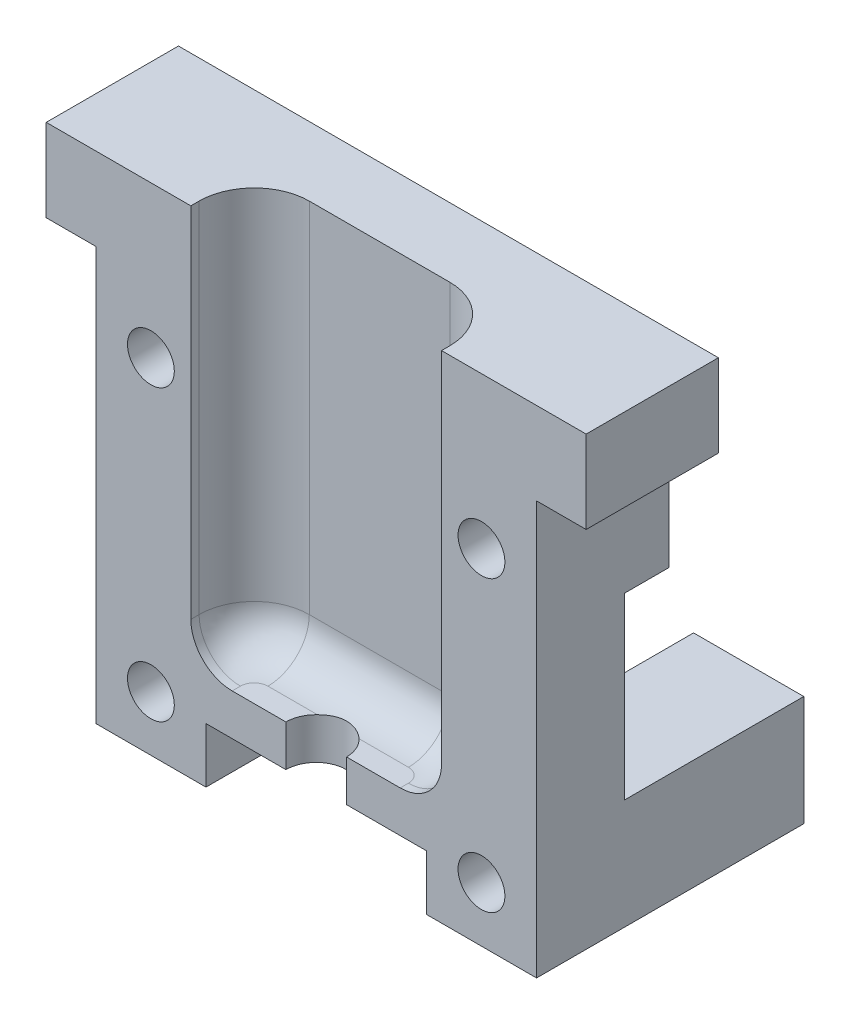
SolidWorks part; units mm, degrees
ref_plane "Спереди" through (0, 0, 0) normal (0, 0, 1) x (1, 0, 0)
ref_plane "Сверху" through (0, 0, 0) normal (0, 1, 0) x (1, 0, 0)
ref_plane "Справа" through (0, 0, 0) normal (1, 0, 0) x (0, 0, -1)
sketch "Эскиз1" plane through (0, 0, 0) normal (0, 0, 1) x (1, 0, 0)
  line L0 (0, 16) -> (0, -16) construction
  line L1 (8, -16) -> (-8, -16)
  line L2 (16, -16) -> (16, 16)
  line L3 (16, 16) -> (-16, 16)
  line L4 (-16, -16) -> (-16, 16)
  line L5 (16, -16) -> (-16, 16) construction
  line L6 (16, 16) -> (-16, -16) construction
  line L7 (-8, -16) -> (-8, -20)
  line L8 (16, -16) -> (16, -20)
  line L9 (16, -20) -> (8, -20)
  line L10 (8, -16) -> (8, -20)
  line L11 (-16, -20) -> (-8, -20)
  line L12 (-16, -16) -> (-16, -20)
  point P0 (0, 0)
  dimension "D1" = 32
  dimension "D2" = 32
  dimension "D3" = 8
  dimension "D4" = 4
extrude "Бобышка-Вытянуть1" add sketch "Эскиз1" along normal blind 16
sketch "Эскиз2" plane through (0, 16, 0) normal (0, 1, 0) x (1, 0, 0)
  line L1 (5.1, -11) -> (-5.1, -11)
  line L2 (9.1, -7) -> (9.1, -5.8)
  line L3 (5.1, -1.8) -> (-5.1, -1.8)
  line L4 (-9.1, -7) -> (-9.1, -5.8)
  line L5 (9.1, -11) -> (-9.1, -1.8) construction
  line L6 (9.1, -1.8) -> (-9.1, -11) construction
  line L7 (16, -16) -> (-16, -16) construction
  arc A0 (5.1, -1.8) -> (9.1, -5.8) centre (5.1, -5.8) cw
  arc A1 (9.1, -7) -> (5.1, -11) centre (5.1, -7) cw
  arc A2 (-5.1, -11) -> (-9.1, -7) centre (-5.1, -7) cw
  arc A3 (-9.1, -5.8) -> (-5.1, -1.8) centre (-5.1, -5.8) cw
  point P0 (0, -6.4)
  dimension "D4" = 4
  dimension "D1" = 9.2
  dimension "D2" = 5
  dimension "D3" = 18.2
extrude "Вырез-Вытянуть1" cut sketch "Эскиз2" against normal blind 29
fillet "Скругление1" radius 3 8 edges at (9.1, -13, 6.4) (7.9284, -13, 9.8284) (0, -13, 11) (-7.9284, -13, 9.8284) (-9.1, -13, 6.4) (-7.9284, -13, 2.9716) (0, -13, 1.8) (7.9284, -13, 2.9716)
sketch "Эскиз3" plane through (0, 0, 0) normal (0, 0, -1) x (-1, 0, 0)
  line L0 (0, 16) -> (0, -16) construction
  line L1 (-16, 16) -> (16, 16) construction
  line L2 (8, -16) -> (-8, -16) construction
  line L5 (-16, 16) -> (16, 16) construction
  circle A0 centre (-12, -16) radius 1.7
  circle A1 centre (-12, 5) radius 1.7
  circle A2 centre (12, 5) radius 1.7
  circle A3 centre (12, -16) radius 1.7
  dimension "D1" = 3.4
  dimension "D4" = 11
  dimension "D5" = 3.4
  dimension "D2" = 12
  dimension "D3" = 32
extrude "Вырез-Вытянуть2" cut sketch "Эскиз3" against normal up to surface (16 mm away) and the other way blind 10 up to face at (0, -10, 16)
sketch "Эскиз4" plane through (0, -16, 0) normal (0, 1, 0) x (1, 0, 0)
  line L0 (-6.1, -5.8) -> (-6.1, -7) construction
  circle A0 centre (0, -6.4) radius 2.2
  point P6 (-6.1, -6.4)
  dimension "D1" = 4.4
extrude "Вырез-Вытянуть3" cut sketch "Эскиз4" along normal up to surface (32 mm away) up to face at (0, 16, 6.4)
sketch "Эскиз5" plane through (0, 0, 16) normal (0, 0, 1) x (1, 0, 0)
  line L0 (0, -16) -> (0, 0) construction
  line L1 (-12, -12.7091) -> (-14.85, -14.3546)
  line L2 (-14.85, -14.3546) -> (-14.85, -17.6454)
  line L3 (-14.85, -17.6454) -> (-12, -19.2909)
  line L4 (-12, -19.2909) -> (-9.15, -17.6454)
  line L5 (-9.15, -17.6454) -> (-9.15, -14.3546)
  line L6 (-9.15, -14.3546) -> (-12, -12.7091)
  line L7 (-8, -16) -> (8, -16) construction
  line L8 (9.15, -14.3546) -> (12, -12.7091)
  line L9 (9.15, -17.6454) -> (9.15, -14.3546)
  line L10 (12, -19.2909) -> (9.15, -17.6454)
  line L11 (14.85, -17.6454) -> (12, -19.2909)
  line L12 (14.85, -14.3546) -> (14.85, -17.6454)
  line L13 (12, -12.7091) -> (14.85, -14.3546)
  circle A0 centre (-12, -16) radius 2.85 construction
  circle A1 centre (12, -16) radius 2.85 construction
  dimension "D1" = 5.7
extrude "Вырез-Вытянуть4" cut sketch "Эскиз5" against normal blind 3
sketch "Эскиз6" plane through (0, 0, 0) normal (0, 0, -1) x (-1, 0, 0)
  line L0 (0, 0) -> (0, -16) construction
  line L1 (-16, -20) -> (-8, -20)
  line L2 (-16, -20) -> (-16, -12)
  line L3 (-16, -12) -> (-8, -12)
  line L4 (-8, -20) -> (-8, -12)
  line L5 (8, -16) -> (-8, -16) construction
  line L6 (-8, -16) -> (-8, -20) construction
  line L7 (8, -20) -> (8, -12)
  line L8 (16, -12) -> (8, -12)
  line L9 (16, -20) -> (16, -12)
  line L10 (16, -20) -> (8, -20)
  circle A0 centre (-12, -16) radius 1.7
  circle A1 centre (-12, -16) radius 1.7 construction
  circle A2 centre (12, -16) radius 1.7
extrude "Бобышка-Вытянуть2" add sketch "Эскиз6" along normal blind 13
sketch "Эскиз8" plane through (0, 16, 0) normal (0, 1, 0) x (1, 0, 0)
  line L2 (19.6, -16) -> (-19.6, -16)
  line L3 (19.6, -16) -> (19.6, 3.2)
  line L4 (19.6, 3.2) -> (-19.6, 3.2)
  line L5 (-19.6, -16) -> (-19.6, 3.2)
  line L6 (19.6, -16) -> (-19.6, 3.2) construction
  line L7 (19.6, 3.2) -> (-19.6, -16) construction
  line L19 (-9.1, -5.8) -> (-9.1, -7)
  line L20 (-5.1, -11) -> (5.1, -11)
  line L21 (9.1, -7) -> (9.1, -5.8)
  line L22 (5.1, -1.8) -> (-5.1, -1.8)
  line L23 (-9.1, -5.8) -> (-9.1, -7)
  line L24 (-5.1, -11) -> (5.1, -11)
  line L25 (9.1, -7) -> (9.1, -5.8)
  line L26 (5.1, -1.8) -> (-5.1, -1.8)
  arc A13 (-9.1, -7) -> (-5.1, -11) centre (-5.1, -7) ccw
  arc A14 (9.1, -5.8) -> (5.1, -1.8) centre (5.1, -5.8) ccw
  arc A15 (5.1, -11) -> (9.1, -7) centre (5.1, -7) ccw
  arc A16 (-5.1, -1.8) -> (-9.1, -5.8) centre (-5.1, -5.8) ccw
  arc A17 (-9.1, -7) -> (-5.1, -11) centre (-5.1, -7) ccw
  arc A18 (9.1, -5.8) -> (5.1, -1.8) centre (5.1, -5.8) ccw
  arc A19 (5.1, -11) -> (9.1, -7) centre (5.1, -7) ccw
  arc A20 (-5.1, -1.8) -> (-9.1, -5.8) centre (-5.1, -5.8) ccw
  point P5 (0, -6.4)
  dimension "D1" = 19.2
  dimension "D2" = 39.2
  dimension "D3" = 0
extrude "Бобышка-Вытянуть3" add sketch "Эскиз8" against normal blind 6
sketch "Эскиз9" plane through (0, 16, 0) normal (0, 1, 0) x (1, 0, 0)
  line L0 (-19.6, 3.2) -> (-19.6, -16) construction
  line L1 (-19.6, -6.4) -> (33.0663, -6.4)
  line L2 (-19.6, -6.4) -> (-19.6, -32.8514)
  line L3 (-19.6, -32.8514) -> (33.0663, -32.8514)
  line L4 (33.0663, -6.4) -> (33.0663, -32.8514)
extrude "Вырез-Вытянуть5" cut sketch "Эскиз9" against normal through all
sketch "Эскиз10" plane through (0, 0, 0) normal (0, 0, -1) x (-1, 0, 0)
  line L0 (-12, 5) -> (-12, 10) construction
  line L1 (-16, 10) -> (16, 10) construction
  line L2 (8, 10) -> (8, 1)
  line L3 (-16, 10) -> (-8, 10)
  line L4 (-16, 10) -> (-16, 1)
  line L5 (0, 0) -> (0, 10) construction
  line L6 (-19.6, 10) -> (19.6, 10) construction
  line L7 (-16, 1) -> (-8, 1)
  line L8 (-8, 10) -> (-8, 1)
  line L9 (16, 1) -> (8, 1)
  line L10 (16, 10) -> (16, 1)
  line L11 (16, 10) -> (8, 10)
  point P15 (-12, 10)
  dimension "D1" = 4
extrude "Бобышка-Вытянуть4" add sketch "Эскиз10" along normal up to surface (3.2 mm away) up to face at (0, 13, -3.2)
sketch "Эскиз11" plane through (0, 0, 6.4) normal (0, 0, 1) x (1, 0, 0)
  circle A0 centre (-12, 5) radius 1.7
  circle A1 centre (12, 5) radius 1.7
  circle A2 centre (12, 5) radius 1.7 construction
extrude "Вырез-Вытянуть6" cut sketch "Эскиз11" against normal up to surface (9.6 mm away) up to face at (0, 8, -3.2)
sketch "Эскиз12" plane through (0, 0, -3.2) normal (0, 0, -1) x (-1, 0, 0)
  line L0 (0, 0) -> (0, 10) construction
  line L1 (-12, 8.2909) -> (-14.85, 6.6454)
  line L2 (-14.85, 6.6454) -> (-14.85, 3.3546)
  line L3 (-14.85, 3.3546) -> (-12, 1.7091)
  line L4 (-12, 1.7091) -> (-9.15, 3.3546)
  line L5 (-9.15, 3.3546) -> (-9.15, 6.6454)
  line L6 (-9.15, 6.6454) -> (-12, 8.2909)
  line L7 (-8, 10) -> (8, 10) construction
  line L8 (9.15, 6.6454) -> (12, 8.2909)
  line L9 (9.15, 3.3546) -> (9.15, 6.6454)
  line L10 (12, 1.7091) -> (9.15, 3.3546)
  line L11 (14.85, 3.3546) -> (12, 1.7091)
  line L12 (14.85, 6.6454) -> (14.85, 3.3546)
  line L13 (12, 8.2909) -> (14.85, 6.6454)
  circle A0 centre (-12, 5) radius 2.85 construction
  circle A1 centre (12, 5) radius 2.85 construction
  dimension "D1" = 5.7
extrude "Вырез-Вытянуть7" cut sketch "Эскиз12" against normal blind 2.5
